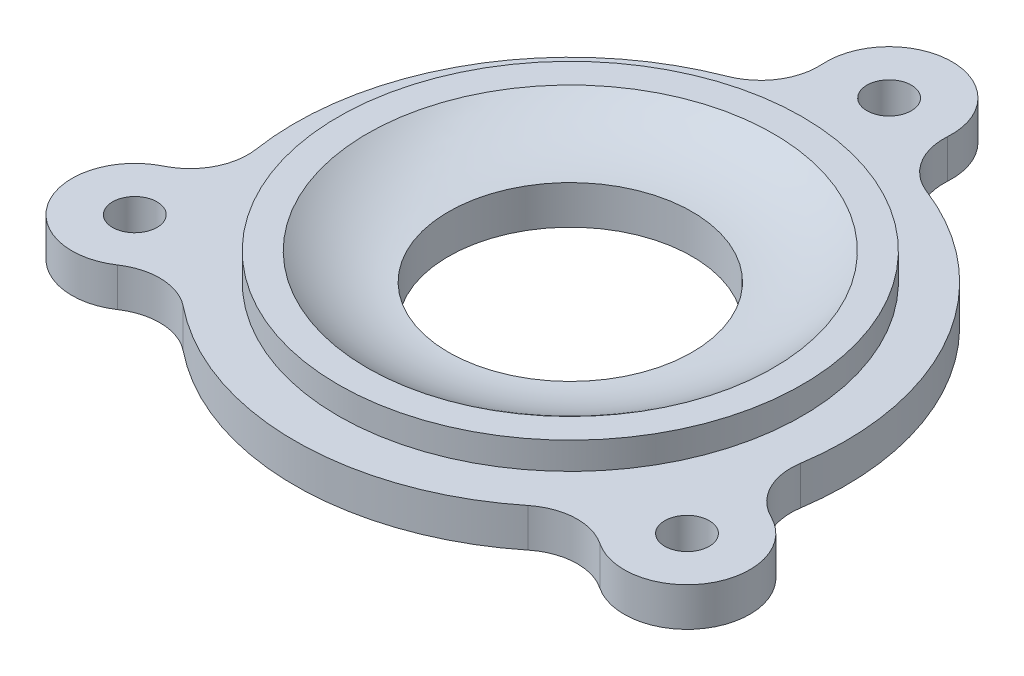
SolidWorks part; units mm, degrees
material "PETG"
ref_plane "Спереди" through (0, 0, 0) normal (0, 0, 1) x (1, 0, 0)
ref_plane "Сверху" through (0, 0, 0) normal (0, 1, 0) x (1, 0, 0)
ref_plane "Справа" through (0, 0, 0) normal (1, 0, 0) x (0, 0, -1)
sketch "Эскиз1" plane through (0, 0, 0) normal (0, 1, 0) x (1, 0, 0)
  line L0 (0, 0) -> (0, 6159.835) construction
  arc A0 (-5.1509, 13.2758) -> (-14.0726, -2.1771) centre (0, 0) ccw
  circle A1 centre (0, 16.49) radius 1.15
  circle A2 centre (0, 0) radius 6.3
  arc A3 (3.2427, 16.273) -> (-3.2427, 16.273) centre (0, 16.49) ccw
  arc A4 (-5.1509, 13.2758) -> (-3.2427, 16.273) centre (-6.236, 16.0726) ccw
  arc A5 (5.1509, 13.2758) -> (3.2427, 16.273) centre (6.236, 16.0726) cw
  arc A6 (14.0726, -2.1771) -> (15.7142, -5.3282) centre (17.0373, -2.6357) ccw
  arc A7 (12.4714, -10.9448) -> (15.7142, -5.3282) centre (14.2808, -8.245) ccw
  arc A8 (8.9217, -11.0987) -> (12.4714, -10.9448) centre (10.8013, -13.4369) cw
  circle A9 centre (14.2808, -8.245) radius 1.15
  arc A10 (-8.9217, -11.0987) -> (-12.4714, -10.9448) centre (-10.8013, -13.4369) ccw
  arc A11 (-15.7142, -5.3282) -> (-12.4714, -10.9448) centre (-14.2808, -8.245) ccw
  arc A12 (-14.0726, -2.1771) -> (-15.7142, -5.3282) centre (-17.0373, -2.6357) cw
  circle A13 centre (-14.2808, -8.245) radius 1.15
  arc A14 (14.0726, -2.1771) -> (5.1509, 13.2758) centre (0, 0) ccw
  arc A15 (-8.9217, -11.0987) -> (8.9217, -11.0987) centre (0, 0) ccw
  point P32 (0, 0)
  dimension "D1" = 2.3
  dimension "D3" = 28.48
  dimension "D4" = 12.6
  dimension "D5" = 3.25
  dimension "D6" = 3
  dimension "D2" = 16.49
  dimension "D7" = 3
extrude "Бобышка-Вытянуть1" add sketch "Эскиз1" along normal blind 2
sketch "Эскиз2" plane through (0, 2, 0) normal (0, 1, 0) x (1, 0, 0)
  circle A0 centre (0, 0) radius 12
  circle A1 centre (0, 0) radius 10.5
  dimension "D1" = 24
  dimension "D2" = 1.5
extrude "Бобышка-Вытянуть2" add sketch "Эскиз2" along normal blind 1.4
fillet "Скругление1" radius 7 1 edges at (0, 2, 10.5)
